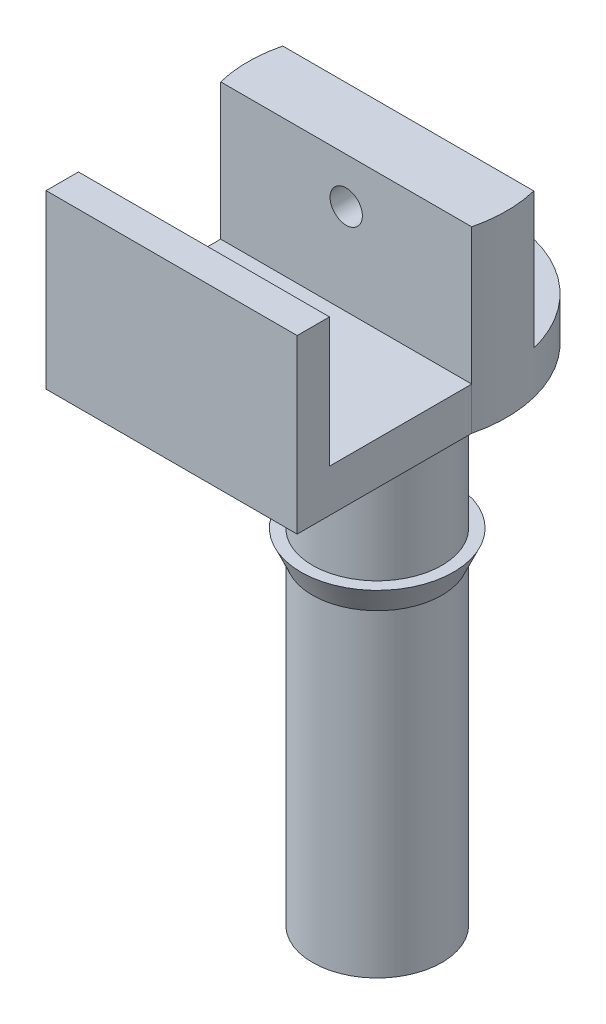
SolidWorks part; units mm, degrees
ref_plane "Front Plane" through (0, 0, 0) normal (0, 0, 1) x (1, 0, 0)
ref_plane "Top Plane" through (0, 0, 0) normal (0, 1, 0) x (1, 0, 0)
ref_plane "Right Plane" through (0, 0, 0) normal (1, 0, 0) x (0, 0, -1)
sketch "Sketch1" plane through (0, 0, 0) normal (0, 1, 0) x (1, 0, 0)
  circle A0 centre (0, 0) radius 12.7
  dimension "D1" = 25.4
extrude "Part that goes into base" add sketch "Sketch1" along normal blind 99.06
sketch "Sketch2" plane through (0, 0, 0) normal (0, 0, 1) x (1, 0, 0)
  line L0 (12.7, 99.06) -> (-12.7, 99.06) construction
  line L1 (12.7, 99.06) -> (-12.7, 99.06)
  line L2 (12.7, 99.06) -> (12.7, 67.564) construction
  line L3 (12.7, 67.564) -> (14.986, 67.564)
  line L4 (14.986, 67.564) -> (12.7, 62.484)
  line L5 (12.7, 62.484) -> (12.7, 67.564)
  line L6 (0, 99.06) -> (0, 52.1662) construction
  dimension "D1" = 31.496
  dimension "D2" = 2.286
  dimension "D3" = 5.08
revolve "Clip in mechanism" add sketch "Sketch2" angle 360 about L6 region at (13.462, 65.8707, 0)
sketch "Sketch3" plane through (0, 99.06, 0) normal (0, 1, 0) x (1, 0, 0)
  circle A0 centre (0, 0) radius 25.4
  dimension "D1" = 50.8
extrude "Boss-Extrude2" add sketch "Sketch3" along normal blind 35.14
ref_plane "Plane1" through (50.8, 0, 0) normal (1, 0, 0) x (0, 0, -1)
sketch "Sketch4" plane through (50.8, 0, 0) normal (1, 0, 0) x (0, 0, -1)
  line L0 (25.4, 134.2) -> (-25.4, 134.2) construction
  line L1 (25.4, 134.2) -> (-25.4, 134.2)
  line L8 (6.096, 134.2) -> (6.096, 107.442)
  line L10 (25.4, 99.06) -> (25.4, 134.2) construction
  line L11 (25.4, 107.442) -> (25.4, 134.2)
  line L12 (6.096, 134.2) -> (25.4, 134.2)
  line L13 (25.4, 107.442) -> (6.096, 107.442)
  line L14 (-25.4, 107.442) -> (-6.096, 107.442)
  line L15 (-25.4, 134.2) -> (-6.096, 134.2)
  line L16 (-25.4, 134.2) -> (-25.4, 107.442)
  line L18 (-6.096, 134.2) -> (-6.096, 107.442)
  dimension "D1" = 8.382
  dimension "D2" = 8.382
  dimension "D4" = 19.304
  dimension "D6" = 19.304
extrude "Cut-Extrude1" cut sketch "Sketch4" against normal through all contours L13 L11 L1 L8 | L18 L1 L16 L14
sketch "Sketch5" plane through (0, 107.442, 0) normal (0, 1, 0) x (1, 0, 0)
  line L0 (-13.191, -27.686) -> (15.1785, -27.686)
  line L1 (24.6576, -6.096) -> (24.6576, -40.386)
  line L2 (-24.6576, -6.096) -> (24.6576, -6.096) construction
  line L3 (-24.6576, -6.096) -> (-24.6576, -40.386)
  line L4 (-24.6576, -40.386) -> (24.6576, -40.386)
  arc A0 (24.6576, -6.096) -> (-24.6576, -6.096) centre (0, 0) cw
  dimension "D1" = 21.59
  dimension "D2" = 34.29
extrude "Boss-Extrude3" add sketch "Sketch5" against normal up to surface (8.382 mm away) contours L3 L4 L1 region at (0, 107.442, 29.7744) up to face at (0, 99.06, 12.7)
sketch "Sketch6" plane through (0, 107.442, 0) normal (0, 1, 0) x (1, 0, 0)
  line L0 (5.2425, -6.096) -> (5.2425, -34.036)
  line L1 (-24.6576, -6.096) -> (24.6576, -6.096) construction
  line L2 (5.2425, -34.036) -> (-7.0201, -34.036)
  line L3 (-7.0201, -34.036) -> (-24.6576, -34.036)
  line L4 (-24.6576, -6.096) -> (-24.6576, -40.386) construction
  line L5 (-24.6576, -34.036) -> (-24.6576, -40.386)
  line L6 (-24.6576, -40.386) -> (24.6576, -40.386)
  line L7 (24.6576, -40.386) -> (24.6576, -34.036)
  line L8 (24.6576, -6.096) -> (24.6576, -40.386) construction
  line L9 (24.6576, -34.036) -> (5.2425, -34.036)
  dimension "D1" = 27.94
extrude "Boss-Extrude4" add sketch "Sketch6" along normal blind 25.4 contours L2 L3 L5 L6 L7 L9
sketch "Sketch7" plane through (0, 0, -6.096) normal (0, 0, -1) x (-1, 0, 0)
  line L0 (0, 134.2) -> (0, 125.31) construction
  line L1 (24.6576, 134.2) -> (-24.6576, 134.2) construction
  circle A0 centre (0, 125.31) radius 3.175
  dimension "D2" = 6.35
  dimension "D1" = 8.89
extrude "Cut-Extrude2" cut sketch "Sketch7" against normal up to surface (12.192 mm away) up to face at (0, 120.821, 6.096)
